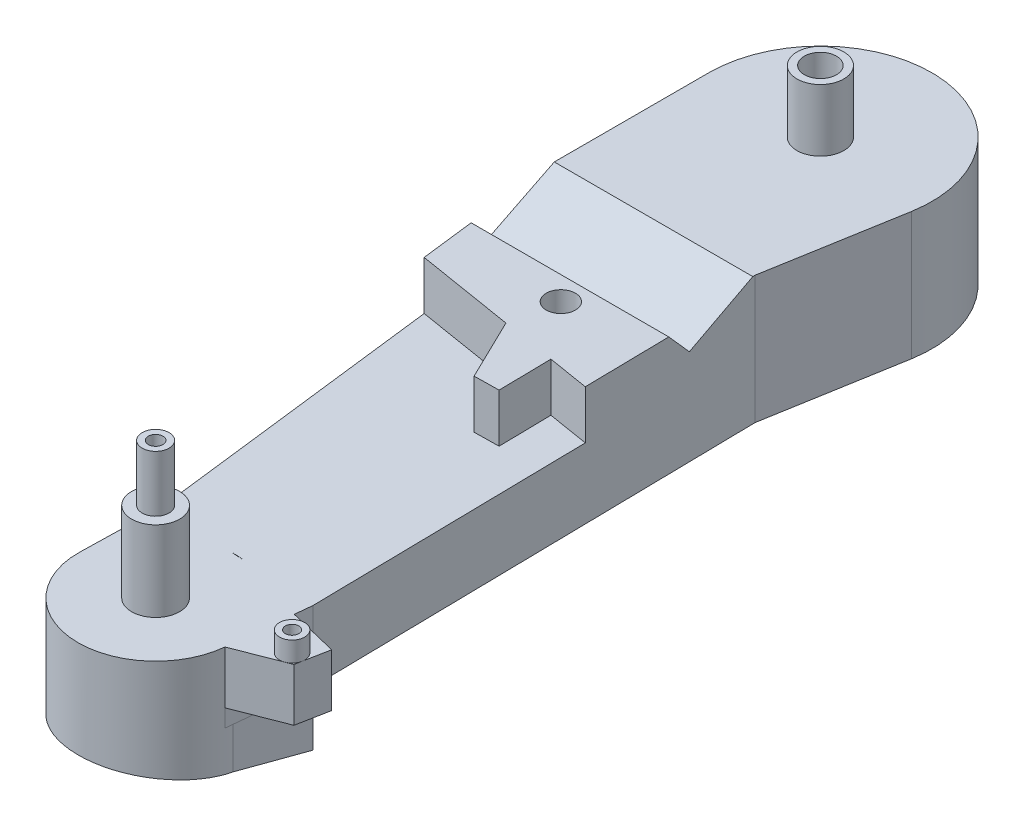
SolidWorks part; units mm, degrees
ref_plane "Front Plane" through (0, 0, 0) normal (0, 0, 1) x (1, 0, 0)
ref_plane "Top Plane" through (0, 0, 0) normal (0, 1, 0) x (1, 0, 0)
ref_plane "Right Plane" through (0, 0, 0) normal (1, 0, 0) x (0, 0, -1)
sketch "Sketch1" plane through (0, 0, 0) normal (0, 1, 0) x (1, 0, 0)
  line L0 (-19.05, 0) -> (-19.05, -26)
  line L1 (-19.05, -26) -> (14.85, -26)
  line L2 (14.85, -26) -> (18.7732, -3.2354)
  line L3 (-19.05, 0) -> (18.7732, -3.2354) construction
  line L4 (-0.1235, -1.4436) -> (0, 0) construction
  line L5 (-19.05, -26) -> (-19.05, -37.7)
  line L6 (-19.05, -37.7) -> (-11.35, -101.1)
  line L7 (-11.35, -101.1) -> (16.15, -102.8)
  line L8 (16.15, -102.8) -> (14.85, -26)
  line L9 (2.4, -101.95) -> (1.5856, -115.1249) construction
  line L10 (-11.35, -101.1) -> (-11.661, -114.8246)
  line L11 (16.15, -102.8) -> (14.7683, -116.4585)
  circle A0 centre (0, 0) radius 19.05
  circle A1 centre (1.5856, -115.1249) radius 13.25
  dimension "D1" = 38.1
  dimension "D10" = 26.5
  dimension "D2" = 33.9
  dimension "D3" = 26
  dimension "D4" = 11.7
  dimension "D5" = 7.7
  dimension "D6" = 63.4
  dimension "D7" = 1.7
  dimension "D8" = 27.5
  dimension "D9" = 13.2
extrude "Boss-Extrude1" add sketch "Sketch1" along normal blind 12 contours A1 L7 L8 L1 L5 L6 | A0 | A0 L0 L1 L2 | A1 L7 L10 | A1 L11 L7 | A1 L7 region at (-2.4498, 0, 19.9131) region at (0, 0, 0) region at (-0.1817, 0, 62.4869) region at (12.8034, 0, 105.6914) region at (-8.385, 0, 104.3816) region at (1.5854, 0, 115.1267)
sketch "Sketch2" plane through (0, 12, 0) normal (0, 1, 0) x (1, 0, 0)
  line L0 (14.85, -26) -> (-19.05, -26)
  line L1 (-19.05, 0) -> (-19.05, -37.7) construction
  line L2 (15.1039, -41) -> (-18.6492, -41)
  line L3 (16.15, -102.8) -> (14.85, -26) construction
  line L4 (-19.05, -26) -> (-18.6492, -41)
  line L5 (15.1039, -41) -> (15.3493, -55.5)
  line L9 (-19.05, -37.7) -> (-18.6492, -41)
  line L10 (-19.05, -37.7) -> (-11.35, -101.1) construction
  line L12 (15.3493, -55.5) -> (-17.54, -50.1329)
  line L13 (-17.54, -50.1329) -> (-18.6492, -41)
  line L14 (8.329, -54.3544) -> (8.4813, -63.3544)
  line L15 (8.4813, -63.3544) -> (4.2813, -63.4255)
  line L16 (4.2813, -63.4255) -> (-0.8496, -52.8565)
  line M12 (16.15, -102.8) -> (14.85, -26)
  line M16 (-19.05, -37.7) -> (-11.35, -101.1)
  dimension "D1" = 15
  dimension "D2" = 14.5
  dimension "D3" = 9.2
  dimension "D4" = 9
  dimension "D5" = 4.2
  dimension "D6" = 9.3
  dimension "D7" = 7
extrude "Boss-Extrude2" add sketch "Sketch2" along normal blind 8.3 contours L12 L2 M12 M16 | L16 L15 L14 L12 region at (-0.1525, 12, 46.9768) region at (4.8452, 12, 57.9195)
sketch "Sketch3" plane through (0, 12, 0) normal (0, 1, 0) x (1, 0, 0)
  line L0 (18.7732, -3.2354) -> (14.85, -26)
  line L1 (14.85, -26) -> (-19.05, -26)
  line L2 (-19.05, 0) -> (-19.05, -37.7) construction
  line L3 (-19.05, -26) -> (-19.05, 0)
  circle A0 centre (0, 0) radius 19.05
  line M4 (14.85, -26) -> (18.7732, -3.2354)
  arc M5 (18.7732, -3.2354) -> (-19.05, 0) centre (0, 0) ccw
  line M6 (-19.05, 0) -> (-19.05, -37.7)
extrude "Boss-Extrude3" add sketch "Sketch3" along normal blind 9.8 contours A0 M5 | A0 L1 M6 M4 region at (-2.4498, 12, 19.9131) region at (0, 12, 0)
chamfer "Chamfer1" distance 10 distance2 20 1 edges at (-2.1, 12, 26) first distance on face at (-2.1, 16.9, 26)
chamfer "Chamfer2" distance 4 distance2 5.8 1 edges at (-1.7727, 14.5, 41) first distance on face at (-5.3577, 17.75, 34.5)
sketch "Sketch4" plane through (0, 12, 0) normal (0, 1, 0) x (1, 0, 0)
  circle A0 centre (1.5856, -115.1249) radius 4.1
  dimension "D1" = 8.2
extrude "Boss-Extrude4" add sketch "Sketch4" along normal blind 13.7
sketch "Sketch5" plane through (0, 25.7, 0) normal (0, 1, 0) x (1, 0, 0)
  circle A0 centre (1.5856, -115.1249) radius 2.3
  dimension "D1" = 4.6
extrude "Boss-Extrude5" add sketch "Sketch5" along normal blind 9.6
sketch "Sketch6" plane through (0, 0, 0) normal (0, -1, 0) x (1, 0, 0)
  circle A0 centre (1.5856, 115.1249) radius 7.75
  dimension "D1" = 15.5
extrude "Cut-Extrude1" cut sketch "Sketch6" against normal offset from surface (4.8 mm away) 20.9 up to face at (1.5856, 25.7, 117.4249)
sketch "Sketch7" plane through (0, 35.3, 0) normal (0, 1, 0) x (1, 0, 0)
  circle A0 centre (1.5856, -115.1249) radius 1.25
  dimension "D1" = 2.5
extrude "Cut-Extrude2" cut sketch "Sketch7" against normal through all
sketch "Sketch8" plane through (0, 0, 0) normal (0, -1, 0) x (1, 0, 0)
  line L0 (-11.6644, 115.1249) -> (-11.35, 101.1)
  line L1 (-11.35, 101.1) -> (-11.661, 114.8246) construction
  line L2 (-11.35, 101.1) -> (16.15, 102.8)
  line L3 (16.15, 102.8) -> (14.8356, 115.1249)
  line L4 (-19.05, 37.7) -> (-11.35, 101.1) construction
  circle A0 centre (1.5856, 115.1249) radius 13.25
  circle M2 centre (1.5856, 115.1249) radius 7.75
  line M4 (1.2522, 101.879) -> (3.5478, 102.021)
  arc M5 (14.7683, 116.4585) -> (-11.661, 114.8246) centre (1.5856, 115.1249) ccw
  dimension "D1" = 26.5
extrude "Boss-Extrude6" add sketch "Sketch8" along normal blind 9.6 contours A0 L0 M4 M5 M2 | A0 L0 L2 | A0 L2 L3 region at (0.9368, 0, 127.9838) region at (-8.3833, 0, 104.3785) region at (12.776, 0, 105.6288)
sketch "Sketch9" plane through (-9.0787, 0, -0.2036) normal (-0.9997, 0, -0.0224) x (-0.0224, 0, 0.9997)
  line L0 (101.329, -9.6) -> (128.3104, -4.6)
  line L1 (128.3104, -4.6) -> (128.3104, -9.6)
  line L2 (128.3104, -9.6) -> (101.329, -9.6)
  line L3 (128.3104, -9.6) -> (128.3104, 12) construction
  dimension "D1" = 5
extrude "Cut-Extrude3" cut sketch "Sketch9" against normal through all
sketch "Sketch10" plane through (0, 20.3, 0) normal (0, 1, 0) x (1, 0, 0)
  line L0 (15.1039, -41) -> (-18.6492, -41) construction
  line L1 (15.3493, -55.5) -> (15.1039, -41) construction
  circle A0 centre (0.6695, -45) radius 2.5
  dimension "D1" = 5
  dimension "D2" = 4
  dimension "D3" = 14.5
extrude "Cut-Extrude4" cut sketch "Sketch10" against normal through all
sketch "Sketch11" plane through (0, 12, 0) normal (0, 1, 0) x (1, 0, 0)
  line L0 (15.8553, -105.7133) -> (14.7683, -116.4585)
  line L1 (16.15, -102.8) -> (14.7683, -116.4585) construction
  line L2 (14.7683, -116.4585) -> (23.2435, -113.1585)
  line L3 (23.2435, -113.1585) -> (24.2922, -107.7594)
  line L4 (24.2922, -107.7594) -> (15.8553, -105.7133)
  dimension "D1" = 10.8
  dimension "D2" = 5.5
  dimension "D3" = 8.6
  dimension "D4" = 8.1
  dimension "D5" = 3.3
extrude "Boss-Extrude7" add sketch "Sketch11" against normal blind 9
sketch "Sketch12" plane through (0, 12, 0) normal (0, 1, 0) x (1, 0, 0)
  line L0 (14.7683, -116.4585) -> (23.2435, -113.1585) construction
  line L1 (23.2435, -113.1585) -> (24.2922, -107.7594) construction
  circle A0 centre (21.3589, -111.585) radius 2.15
  dimension "D1" = 4.3
extrude "Boss-Extrude8" add sketch "Sketch12" along normal blind 3.4
sketch "Sketch13" plane through (0, 15.4, 0) normal (0, 1, 0) x (1, 0, 0)
  circle A0 centre (21.3589, -111.585) radius 1.15
  dimension "D1" = 2.3
extrude "Cut-Extrude5" cut sketch "Sketch13" against normal blind 3.4
sketch "Sketch14" plane through (0, 21.8, 0) normal (0, 1, 0) x (1, 0, 0)
  circle A0 centre (0, 0) radius 4
  dimension "D1" = 8
extrude "Boss-Extrude9" add sketch "Sketch14" along normal blind 10.6 and the other way blind 34.5
sketch "Sketch15" plane through (0, 32.4, 0) normal (0, 1, 0) x (1, 0, 0)
  circle A0 centre (0, 0) radius 2.75
  dimension "D1" = 5.5
extrude "Cut-Extrude6" cut sketch "Sketch15" against normal through all
sketch "Sketch27" plane through (0, 0, 0) normal (0, -1, 0) x (1, 0, 0)
  line L0 (-9.1728, 32.3) -> (5.2492, 32.3)
  line L3 (9.9867, 8.8) -> (-13.2699, 8.8)
  line L7 (9.9867, 8.8) -> (7.6102, 27.5742)
  line L8 (7.6102, 27.5742) -> (7.2334, 30.5512)
  line L10 (-13.2699, 8.8) -> (-11.4408, 27.6364)
  line L11 (-11.4408, 27.6364) -> (-11.1634, 30.4933)
  line L13 (16.15, 102.8) -> (14.85, 26) construction
  arc A0 (5.2492, 32.3) -> (7.2334, 30.5512) centre (5.2492, 30.3) cw
  arc A1 (-9.1728, 32.3) -> (-11.1634, 30.4933) centre (-9.1728, 30.3) ccw
  point P15 (-10.988, 32.3)
  dimension "D2" = 2
  dimension "D1" = 23.5
  dimension "D3" = 14.422
  dimension "D4" = 23.2566
  dimension "D5" = 18.8364
  dimension "D6" = 18.7742
  dimension "D7" = 2.8569
  dimension "D8" = 2.977
  dimension "D9" = 9.706
  dimension "D10" = 6.3
extrude "Cut-Extrude11" cut sketch "Sketch27" against normal blind 14
